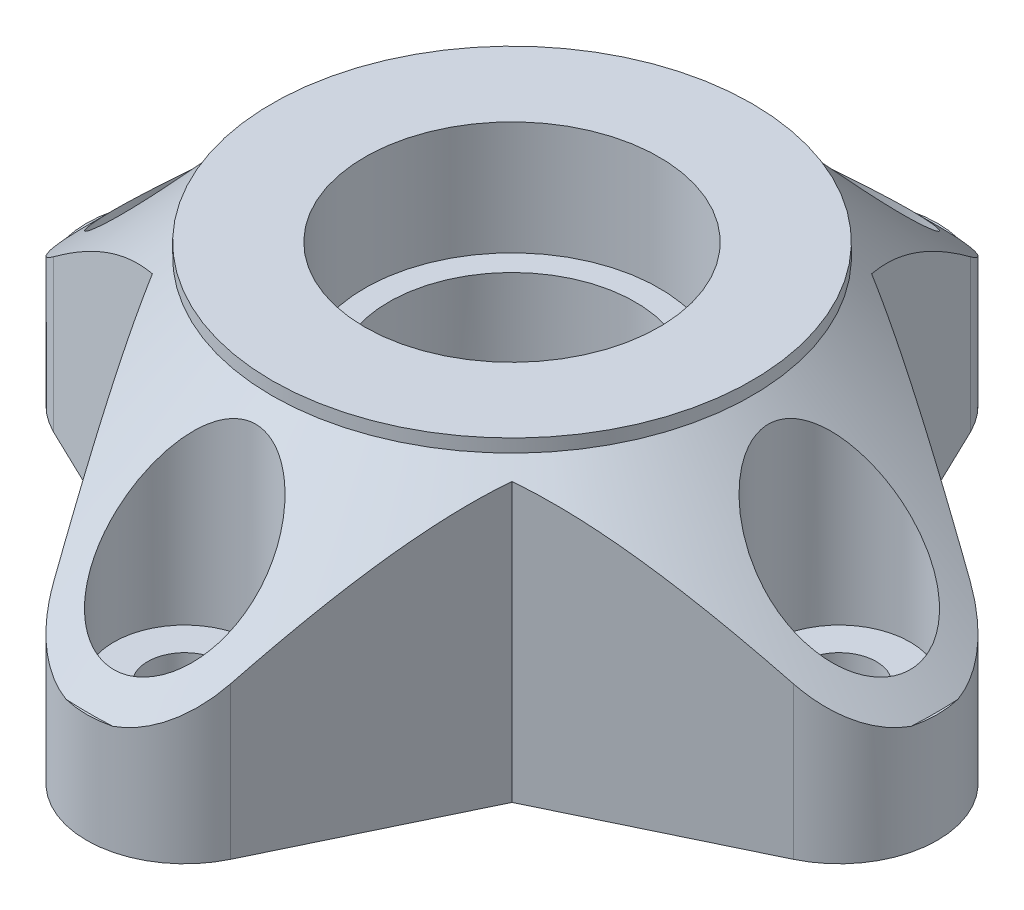
SolidWorks part; units mm, degrees
ref_plane "Спереди" through (0, 0, 0) normal (0, 0, 1) x (1, 0, 0)
ref_plane "Сверху" through (0, 0, 0) normal (0, 1, 0) x (1, 0, 0)
ref_plane "Справа" through (0, 0, 0) normal (1, 0, 0) x (0, 0, -1)
sketch "Эскиз1" plane through (0, 0, 0) normal (0, 1, 0) x (1, 0, 0)
  circle A0 centre (0, 0) radius 11
  dimension "D1" = 22
extrude "тело" add sketch "Эскиз1" along normal blind 14
sketch "Эскиз2" plane through (0, 14, 0) normal (0, 1, 0) x (1, 0, 0)
  circle A0 centre (0, 0) radius 6.75
  dimension "D1" = 13.5
extrude "углубление верхнего подшипника" cut sketch "Эскиз2" against normal blind 5.2
sketch "Эскиз3" plane through (0, 0, 0) normal (0, -1, 0) x (1, 0, 0)
  circle A0 centre (0, 0) radius 6.75
  dimension "D1" = 13.5
extrude "углубление нижнего подшипника" cut sketch "Эскиз3" against normal blind 5.2
sketch "Эскиз4" plane through (0, 8.8, 0) normal (0, 1, 0) x (1, 0, 0)
  circle A0 centre (0, 0) radius 5.65
  dimension "D1" = 11.3
extrude "сквозное отверстие" cut sketch "Эскиз4" against normal through all
sketch "Эскиз5" plane through (0, 0, 0) normal (0, -1, 0) x (1, 0, 0)
  line L0 (-16.95, 4.0556) -> (-4.7667, 9.9136)
  line L2 (-16.95, -4.0556) -> (-4.7667, -9.9136)
  arc A0 (-16.95, 4.0556) -> (-16.95, -4.0556) centre (-15, 0) ccw
  circle A1 centre (-15, 0) radius 1.7
  circle A2 centre (0, 0) radius 11 construction
  arc A3 (-4.7667, 9.9136) -> (-4.7667, -9.9136) centre (0, 0) ccw
  circle M4 centre (0, 0) radius 11
  dimension "D2" = 4.5
  dimension "D3" = 3.4
  dimension "D1" = 15
extrude "крепление к этажу" add sketch "Эскиз5" against normal blind 5 contours A1 L0 A0 L2 M4 region at (-10.7513, 0, 6.7619)
pattern_circular "Круговой массив2" count 4 over 360 about axis through (0, 0, 0) along (0, 1, 0) of "крепление к этажу"
chamfer "Фаска2" distance 8.4 distance2 8.4 1 edges at (0, 5, -11)
sketch "Эскиз6" plane through (0, 0, 0) normal (0, -1, 0) x (1, 0, 0)
  circle A0 centre (0, 15) radius 3.25
  circle A1 centre (-15, 0) radius 3.25
  circle A2 centre (15, 0) radius 3.25
  circle A3 centre (0, -15) radius 3.25
  dimension "D1" = 6.5
extrude "Углубления под шляпки" cut sketch "Эскиз6" against normal through all from offset 4 offset against normal yes
